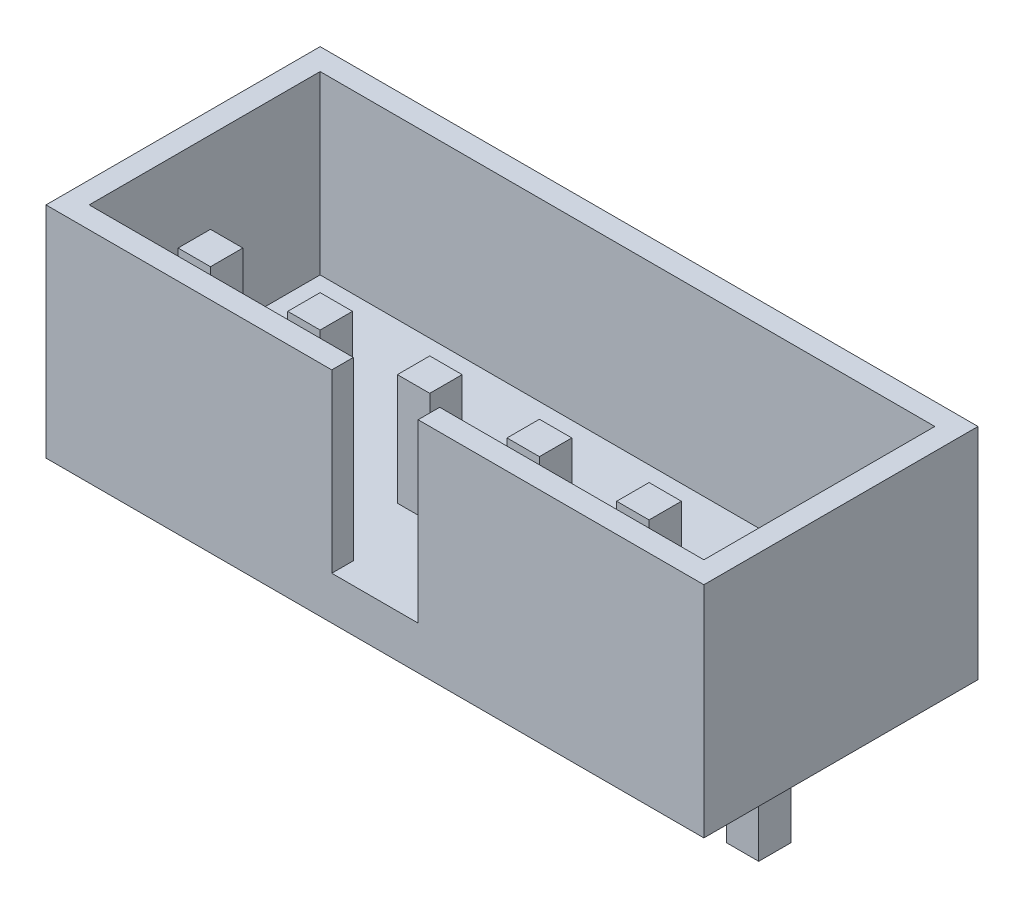
SolidWorks part; units mm, degrees
ref_plane "前视基准面" through (0, 0, 0) normal (0, 0, 1) x (1, 0, 0)
ref_plane "上视基准面" through (0, 0, 0) normal (0, 1, 0) x (1, 0, 0)
ref_plane "右视基准面" through (0, 0, 0) normal (1, 0, 0) x (0, 0, -1)
sketch "草图1" plane through (0, 0, 0) normal (0, 1, 0) x (1, 0, 0)
  line L0 (0, 7.1914) -> (0, -5.4429) construction
  line L1 (-7.62, 3.175) -> (7.62, 3.175)
  line L2 (-7.62, 3.175) -> (-7.62, -3.175)
  line L3 (-7.62, -3.175) -> (7.62, -3.175)
  line L4 (7.62, 3.175) -> (7.62, -3.175)
  line L5 (-10.6234, 0) -> (16.1963, 0) construction
  dimension "D1" = 15.24
  dimension "D2" = 6.35
extrude "拉伸1" add sketch "草图1" along normal blind 5.08
sketch "草图2" plane through (0, 5.08, 0) normal (0, 1, 0) x (-1, 0, 0)
  line L8 (7.12, -2.675) -> (7.12, 2.675)
  line L9 (7.12, 2.675) -> (-7.12, 2.675)
  line L10 (-7.12, 2.675) -> (-7.12, -2.675)
  line L11 (-7.12, -2.675) -> (7.12, -2.675)
  line L12 (7.12, -2.675) -> (7.12, 2.675)
  line L13 (7.12, 2.675) -> (-7.12, 2.675)
  line L14 (-7.12, 2.675) -> (-7.12, -2.675)
  line L15 (-7.12, -2.675) -> (7.12, -2.675)
  dimension "D1" = 0.5
extrude "切除-拉伸1" cut sketch "草图2" against normal offset from surface (4.08 mm away) 1 up to face at (0, 0, 0)
sketch "草图3" plane through (0, 0, 3.175) normal (0, 0, 1) x (1, 0, 0)
  line L0 (-7.62, 5.08) -> (7.62, 5.08) construction
  line L1 (-1, 5.08) -> (1, 5.08)
  line L2 (-1, 5.08) -> (-1, 1)
  line L3 (-1, 1) -> (1, 1)
  line L4 (1, 5.08) -> (1, 1)
  line L5 (7.12, 1) -> (-7.12, 1) construction
  line L6 (0, -1.5083) -> (0, 12.2426) construction
  dimension "D1" = 2
extrude "切除-拉伸2" cut sketch "草图3" against normal blind 1
sketch "草图4" plane through (0, 0, 0) normal (0, -1, 0) x (1, 0, 0)
  line L0 (7.6775, 0.635) -> (-8.5467, 0.635) construction
  line L1 (-7.62, 3.175) -> (7.62, 3.175) construction
  line L2 (0, -3.6953) -> (0, 4.0669) construction
  line L3 (-1.27, 2.1009) -> (-1.27, -0.7012) construction
  line L4 (-1.645, 1.01) -> (-0.895, 1.01)
  line L5 (-1.645, 1.01) -> (-1.645, 0.26)
  line L6 (-1.645, 0.26) -> (-0.895, 0.26)
  line L7 (-0.895, 1.01) -> (-0.895, 0.26)
  line L8 (0.895, 1.01) -> (1.645, 1.01)
  line L9 (0.895, 1.01) -> (0.895, 0.26)
  line L10 (0.895, 0.26) -> (1.645, 0.26)
  line L11 (1.645, 1.01) -> (1.645, 0.26)
  line L12 (2.54, -3.6953) -> (2.54, 4.0669) construction
  line L13 (3.435, 1.01) -> (4.185, 1.01)
  line L14 (3.435, 1.01) -> (3.435, 0.26)
  line L15 (3.435, 0.26) -> (4.185, 0.26)
  line L16 (4.185, 1.01) -> (4.185, 0.26)
  line L17 (5.08, -3.6953) -> (5.08, 4.0669) construction
  line L18 (5.975, 1.01) -> (6.725, 1.01)
  line L19 (5.975, 1.01) -> (5.975, 0.26)
  line L20 (5.975, 0.26) -> (6.725, 0.26)
  line L21 (6.725, 1.01) -> (6.725, 0.26)
  line L22 (7.62, -3.6953) -> (7.62, 4.0669) construction
  line L23 (-4.185, 1.01) -> (-3.435, 1.01)
  line L24 (-4.185, 1.01) -> (-4.185, 0.26)
  line L25 (-4.185, 0.26) -> (-3.435, 0.26)
  line L26 (-3.435, 1.01) -> (-3.435, 0.26)
  line L27 (-3.81, 2.1009) -> (-3.81, -0.7012) construction
  line L28 (5.1375, 0.635) -> (-11.0867, 0.635) construction
  line L29 (-6.725, 1.01) -> (-5.975, 1.01)
  line L30 (-6.725, 1.01) -> (-6.725, 0.26)
  line L31 (-6.725, 0.26) -> (-5.975, 0.26)
  line L32 (-5.975, 1.01) -> (-5.975, 0.26)
  line L33 (-6.35, 2.1009) -> (-6.35, -0.7012) construction
  line L34 (2.5975, 0.635) -> (-13.6267, 0.635) construction
  dimension "D1" = 2.54
  dimension "D2" = 0.75
  dimension "D3" = 0.75
  dimension "D4" = 1.27
  dimension "D5" = 4
  dimension "D6" = 3
extrude "拉伸2" add sketch "草图4" along normal blind 2 and the other way offset from surface 1.5 other way up to face at (0, 5.08, 0.975)
